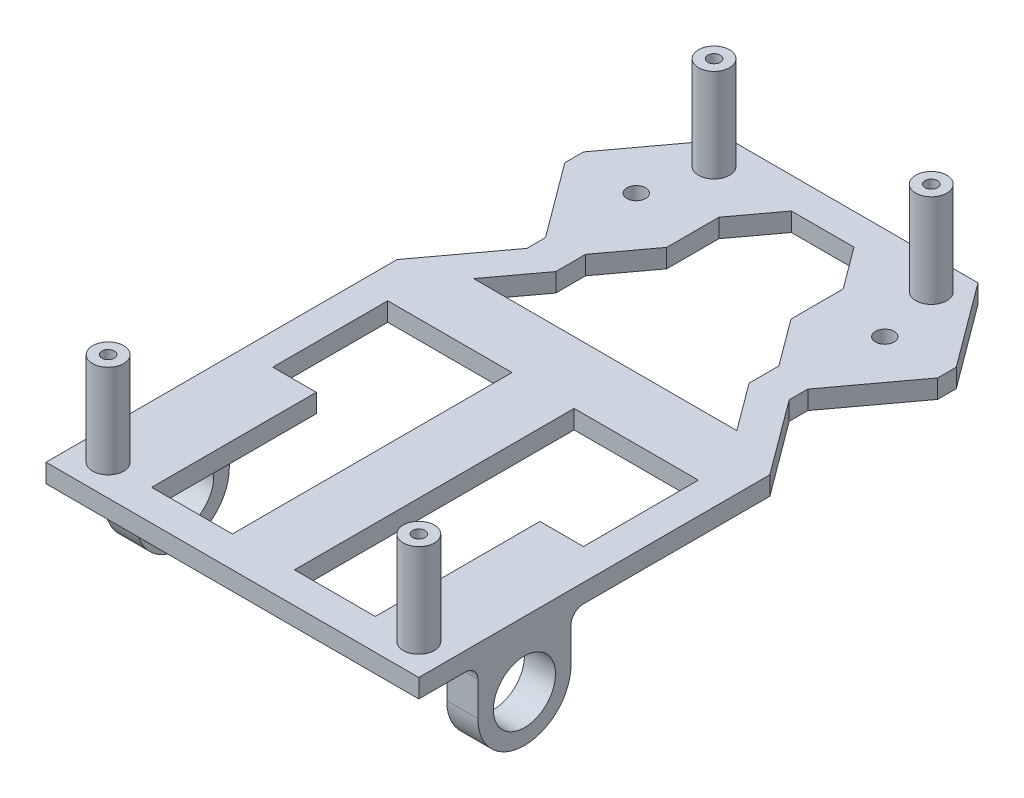
SolidWorks part; units mm, degrees
ref_plane "Front Plane" through (0, 0, 0) normal (0, 0, 1) x (1, 0, 0)
ref_plane "Top Plane" through (0, 0, 0) normal (0, 1, 0) x (1, 0, 0)
ref_plane "Right Plane" through (0, 0, 0) normal (1, 0, 0) x (0, 0, -1)
sketch "Sketch2" plane through (0, 0, 0) normal (0, 1, 0) x (1, 0, 0)
  line L0 (-30, 85) -> (30, 85) construction
  line L1 (30, 0) -> (-30, 0)
  line L2 (30, 0) -> (30, 56.5)
  line L3 (20, 100) -> (-20, 100)
  line L4 (-30, 0) -> (-30, 56.5)
  line L5 (21.1111, 71.5) -> (21.1111, 68.5)
  line L6 (21.1111, 68.5) -> (30, 56.5)
  line L7 (0, 0) -> (0, 100) construction
  line L8 (-30, 86.5) -> (-20, 100)
  line L9 (-30, 83.5) -> (-21.1111, 71.5)
  line L10 (-21.1111, 68.5) -> (-30, 56.5)
  line L11 (-21.1111, 71.5) -> (-21.1111, 68.5)
  line L12 (30, 83.5) -> (21.1111, 71.5)
  line L13 (30, 86.5) -> (20, 100)
  line L14 (30, 83.5) -> (30, 86.5)
  line L15 (-30, 83.5) -> (-30, 86.5)
  circle A0 centre (-20, 85) radius 1.5
  circle A1 centre (20, 85) radius 1.5
  point P0 (0, 0)
  point P1 (0, 50)
  point P3 (0, 0)
  point P17 (0, 0)
  point P22 (0, 0)
  point P23 (0, 0)
  point P24 (0, 0)
  dimension "D4" = 3
  dimension "D1" = 40
  dimension "D2" = 100
  dimension "D3" = 15
  dimension "D5" = 10
  dimension "D6" = 3
  dimension "D7" = 3
  dimension "D8" = 106.942
  dimension "D9" = 28.5
  dimension "D10" = 50
extrude "Boss-Extrude1" add sketch "Sketch2" along normal blind 3
sketch "Sketch5" plane through (0, 0, 0) normal (0, -1, 0) x (1, 0, 0)
  line L0 (-30, -17) -> (30, -17) construction
  line L1 (-30, -56.5) -> (-30, 0) construction
  line L2 (30, 0) -> (30, -56.5) construction
  line L3 (-30, 0) -> (30, 0) construction
  line L4 (0, 0) -> (0, -17) construction
  line L5 (-25, -9.5) -> (-30, -9.5)
  line L6 (-25, -9.5) -> (-25, -24.5)
  line L7 (-25, -24.5) -> (-30, -24.5)
  line L8 (-30, -9.5) -> (-30, -24.5)
  line L9 (-25, -9.5) -> (-30, -24.5) construction
  line L10 (-25, -24.5) -> (-30, -9.5) construction
  line L11 (25, -24.5) -> (30, -24.5)
  line L12 (30, -9.5) -> (30, -24.5)
  line L13 (25, -9.5) -> (30, -9.5)
  line L14 (25, -9.5) -> (25, -24.5)
  point P8 (-27.5, -17)
  dimension "D1" = 17
  dimension "D2" = 5
  dimension "D3" = 15
extrude "Boss-Extrude3" add sketch "Sketch5" along normal blind 15
sketch "Sketch6" plane through (-30, 0, 0) normal (-1, 0, 0) x (0, 0, 1)
  line L0 (-9.5, -15) -> (-24.5, -15) construction
  line L1 (-56.5, 0) -> (-24.5, 0) construction
  circle A0 centre (-17, -7.5) radius 5
  point P2 (0, 0)
  point P5 (-17, -15)
  dimension "D1" = 10
  dimension "D2" = 7.5
extrude "Cut-Extrude1" cut sketch "Sketch6" against normal through all both and the other way through all
fillet "Fillet1" radius 7.5 4 edges at (27.5, -15, -9.5) (27.5, -15, -24.5) (-27.5, -15, -24.5) (-27.5, -15, -9.5)
fillet "Fillet2" radius 2 6 edges at (25, 0, -17) (-25, 0, -17) (27.5, 0, -9.5) (27.5, 0, -24.5) (-27.5, 0, -24.5) (-27.5, 0, -9.5)
sketch "Sketch7" plane through (0, 3, 0) normal (0, 1, 0) x (1, 0, 0)
  line L0 (0, 0) -> (0, 100) construction
  line L1 (20, 100) -> (-20, 100) construction
  line L2 (-30, 0) -> (30, 0) construction
  line L3 (30, 0) -> (30, 56.5) construction
  line L4 (30, 86.5) -> (20, 100) construction
  circle A0 centre (25, 5) radius 2.5
  circle A1 centre (-25, 5) radius 2.5
  circle A2 centre (17.4814, 95) radius 2.5
  circle A3 centre (-17.4814, 95) radius 2.5
  circle A4 centre (25, 5) radius 1
  circle A5 centre (-25, 5) radius 1
  circle A6 centre (17.4814, 95) radius 1
  circle A7 centre (-17.4814, 95) radius 1
  dimension "D1" = 5
  dimension "D4" = 5
  dimension "D7" = 2
  dimension "D8" = 2
  dimension "D2" = 5
  dimension "D3" = 5
  dimension "D5" = 5
  dimension "D6" = 5
extrude "Boss-Extrude4" add sketch "Sketch7" along normal blind 15
sketch "Sketch8" plane through (0, 0, 0) normal (0, -1, 0) x (1, 0, 0)
  line L0 (0, 0) -> (0, -100) construction
  line L1 (20, -100) -> (-20, -100) construction
  line L2 (-18, -5) -> (-18, -31.5)
  line L4 (-15.5553, -67.6002) -> (-15.5553, -72.3998)
  line L6 (-21.1111, -71.5) -> (-21.1111, -68.5) construction
  line L11 (-10, -79.8994) -> (-15.5553, -72.3998)
  line L13 (-18, -5) -> (18, -5)
  line L14 (-20, -100) -> (-30, -86.5) construction
  line L15 (-23, -7.5) -> (-23, -26.5) construction
  line L16 (-18, -31.5) -> (-25, -31.5)
  line L17 (-25, -31.5) -> (-25, -54.8499)
  line L18 (-25, -54.8499) -> (-15.5553, -67.6002)
  line L19 (-21.1111, -68.5) -> (-30, -56.5) construction
  line L20 (-23, -26.5) -> (-30, -26.5) construction
  line L21 (-30, -56.5) -> (-30, -26.5) construction
  line L22 (-10, -79.8994) -> (-10, -88.2996)
  line L23 (-30, 0) -> (30, 0) construction
  line L24 (25, -54.8499) -> (15.5553, -67.6002)
  line L25 (25, -31.5) -> (25, -54.8499)
  line L26 (18, -31.5) -> (25, -31.5)
  line L27 (10, -79.8994) -> (15.5553, -72.3998)
  line L28 (15.5553, -67.6002) -> (15.5553, -72.3998)
  line L29 (18, -5) -> (18, -31.5)
  line L32 (-30, -86.5) -> (-30, -83.5) construction
  line L33 (-10, -88.2996) -> (-5.0367, -95)
  line L34 (-5.0367, -95) -> (5.0367, -95)
  line L35 (10, -88.2996) -> (5.0367, -95)
  line L36 (10, -79.8994) -> (10, -88.2996)
  point P17 (0, -5)
  point P28 (-21.1111, -70)
  point P29 (-15.5553, -70)
  point P37 (0, -5)
  point P39 (-20, -85)
  point P40 (0, -95)
  point P44 (0, -95)
  dimension "D1" = 5
  dimension "D2" = 5
  dimension "D3" = 5
  dimension "D4" = 5
  dimension "D5" = 5
  dimension "D6" = 5
  dimension "D7" = 20
  dimension "D8" = 20
  dimension "D9" = 15
extrude "Cut-Extrude2" cut sketch "Sketch8" against normal through all both and the other way through all
sketch "Sketch9" plane through (0, 0, 0) normal (0, 1, 0) x (1, 0, 0)
  line L0 (-25, 50) -> (-5, 50)
  line L1 (25, 54.8499) -> (21.1851, 60)
  line L3 (21.1851, 60) -> (-21.1851, 60)
  line L4 (20, 100) -> (-20, 100) construction
  line L5 (-21.1851, 60) -> (-25, 54.8499)
  line L6 (-15.5553, 67.6002) -> (-25, 54.8499) construction
  line L7 (25, 54.8499) -> (15.5553, 67.6002) construction
  line L8 (-25, 54.8499) -> (-25, 50)
  line L9 (-25, 54.8499) -> (-25, 31.5) construction
  line L10 (25, 54.8499) -> (25, 50)
  line L11 (25, 31.5) -> (25, 54.8499) construction
  line L13 (5, 0) -> (-5, 0)
  line L14 (5, 0) -> (5, 50)
  line L16 (-5, 0) -> (-5, 50)
  line L17 (5, 0) -> (-5, 50) construction
  line L18 (5, 50) -> (-5, 0) construction
  line L19 (-30, 0) -> (30, 0) construction
  line L20 (5, 50) -> (25, 50)
  point P1 (0, 25)
  point P25 (0, 0)
  dimension "D1" = 10
  dimension "D2" = 40
  dimension "D3" = 10
extrude "Boss-Extrude5" add sketch "Sketch9" along normal up to surface (3 mm away) up to face at (0, 3, -58.4499)
